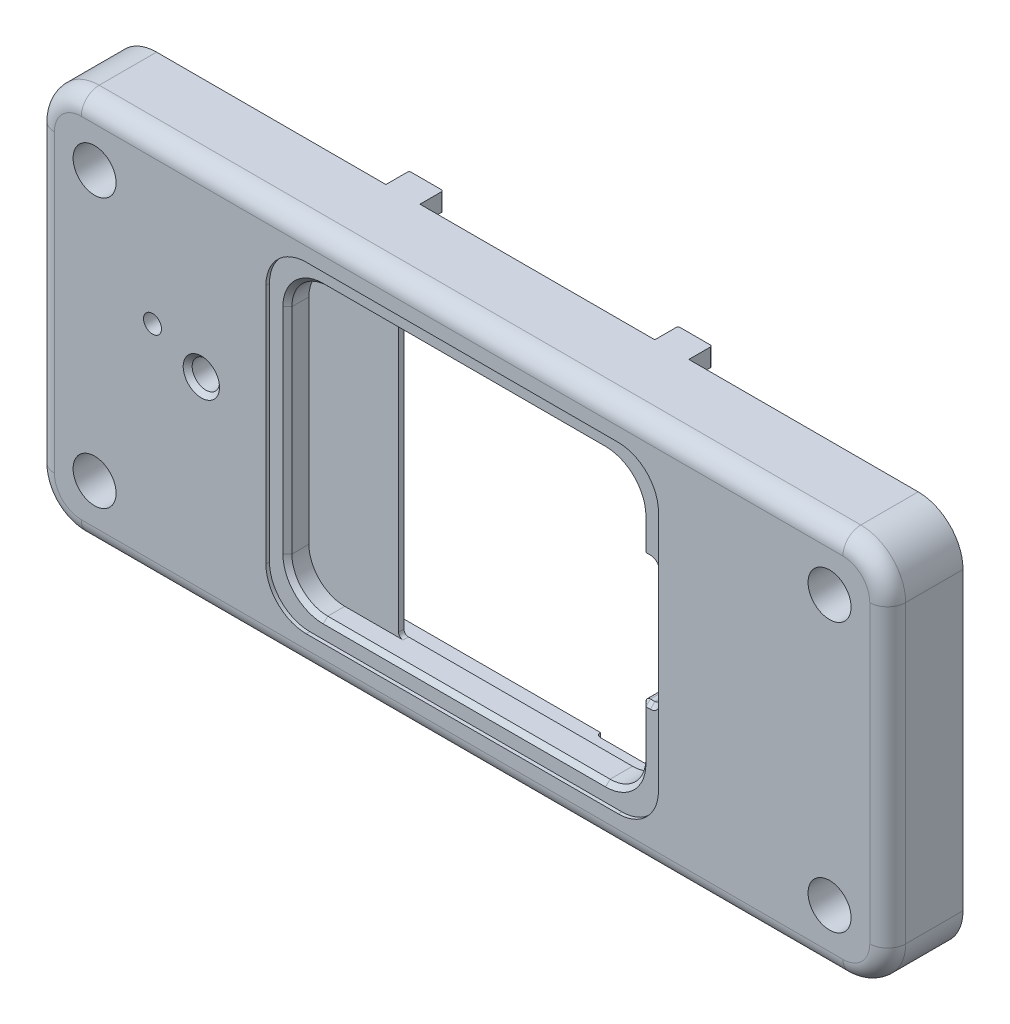
SolidWorks part; units mm, degrees
ref_plane "前视基准面" through (0, 0, 0) normal (0, 0, 1) x (1, 0, 0)
ref_plane "上视基准面" through (0, 0, 0) normal (0, 1, 0) x (1, 0, 0)
ref_plane "右视基准面" through (0, 0, 0) normal (1, 0, 0) x (0, 0, -1)
other "Configuration Table"
sketch "草图2" plane through (0, 0, 0) normal (0, 0, 1) x (1, 0, 0)
  line L0 (81.4875, 0.4873) -> (62.0001, 0.4873) construction
  line L1 (-2.4873, 2.4873) -> (92.4875, 2.4873)
  line L2 (-2.4873, 2.4873) -> (-2.4873, -40.4874)
  line L3 (-2.4873, -40.4874) -> (92.4875, -40.4874)
  line L4 (92.4875, 2.4873) -> (92.4875, -40.4874)
  line L5 (-0.4873, 0.4873) -> (90.4875, 0.4873)
  line L6 (-0.4873, 0.4873) -> (-0.4873, -38.4874)
  line L7 (-0.4873, -38.4874) -> (90.4875, -38.4874)
  line L8 (90.4875, 0.4873) -> (90.4875, -38.4874)
  line L9 (-0.4873, -8.5127) -> (-0.4873, -29.4874) construction
  line L10 (8.5127, -38.4874) -> (52.0301, -38.4874) construction
  line L11 (90.4875, -29.4874) -> (90.4875, -8.5127) construction
  point P10 (0, 0)
  point P13 (0, 0)
extrude "凸台-拉伸1" add sketch "草图2" along normal blind 5
sketch "草图3" plane through (0, 0, 5) normal (0, 0, 1) x (1, 0, 0)
  line L1 (-2.4873, 2.4873) -> (92.4875, 2.4873)
  line L2 (-2.4873, 2.4873) -> (-2.4873, -40.4874)
  line L3 (-2.4873, -40.4874) -> (92.4875, -40.4874)
  line L4 (92.4875, 2.4873) -> (92.4875, -40.4874)
extrude "凸台-拉伸2" add sketch "草图3" along normal blind 3.4
sketch "草图4" plane through (0, 0, 8.4) normal (0, 0, 1) x (1, 0, 0)
  line L0 (0.0127, -9) -> (0.0127, -2) construction
  line L1 (23.1127, -1.0627) -> (66.9127, -1.0627)
  line L2 (23.1127, -1.0627) -> (23.1127, -36.9627)
  line L3 (23.1127, -36.9627) -> (66.9127, -36.9627)
  line L4 (66.9127, -1.0627) -> (66.9127, -36.9627)
  line L5 (2, -0.0127) -> (88.0002, -0.0127) construction
  dimension "D1" = 35.9
  dimension "D2" = 43.8
  dimension "D3" = 23.1
  dimension "D4" = 1.05
extrude "切除-拉伸1" cut sketch "草图4" against normal blind 0.4
fillet "圆角1" radius 4.5 4 edges at (66.9127, -36.9627, 8.2) (23.1127, -36.9627, 8.2) (66.9127, -1.0627, 8.2) (23.1127, -1.0627, 8.2)
sketch "草图5" plane through (0, 0, 8) normal (0, 0, 1) x (1, 0, 0)
  line L0 (62.4127, -1.0627) -> (27.6127, -1.0627) construction
  line L1 (25.1127, -3.0627) -> (64.6127, -3.0627)
  line L2 (25.1127, -3.0627) -> (25.1127, -34.9627)
  line L3 (25.1127, -34.9627) -> (64.6127, -34.9627)
  line L4 (64.6127, -3.0627) -> (64.6127, -11.0627)
  line L5 (27.6127, -36.9627) -> (62.4127, -36.9627) construction
  line L6 (23.1127, -5.5627) -> (23.1127, -32.4627) construction
  line L7 (66.9127, -32.4627) -> (66.9127, -5.5627) construction
  line L8 (64.6127, -11.0627) -> (66.1127, -11.0627)
  line L9 (66.1127, -11.0627) -> (66.1127, -24.9627)
  line L10 (66.1127, -24.9627) -> (64.6127, -24.9627)
  line L11 (64.6127, -24.9627) -> (64.6127, -34.9627)
  dimension "D1" = 2
  dimension "D2" = 2
  dimension "D3" = 2
  dimension "D4" = 2.3
  dimension "D5" = 10
  dimension "D6" = 8
  dimension "D7" = 1.5
extrude "切除-拉伸2" cut sketch "草图5" against normal blind 2.4
sketch "草图6" plane through (0, 0, 5.6) normal (0, 0, 1) x (1, 0, 0)
  line L7 (64.6127, -3.0627) -> (25.1127, -3.0627) construction
  line L8 (35.1127, -3.0627) -> (64.6127, -3.0627)
  line L9 (35.1127, -3.0627) -> (35.1127, -34.9627)
  line L10 (35.1127, -34.9627) -> (64.6127, -34.9627)
  line L11 (64.6127, -3.0627) -> (64.6127, -11.0627)
  line L12 (25.1127, -3.0627) -> (25.1127, -34.9627) construction
  line L13 (64.6127, -11.0627) -> (64.6127, -3.0627) construction
  line L14 (64.6127, -11.0627) -> (66.1127, -11.0627)
  line L15 (66.1127, -11.0627) -> (66.1127, -24.9627)
  line L16 (66.1127, -24.9627) -> (64.6127, -24.9627)
  line L17 (64.6127, -24.9627) -> (64.6127, -34.9627)
  dimension "D1" = 10
extrude "切除-拉伸3" cut sketch "草图6" against normal blind 0.6
fillet "圆角2" radius 4 4 edges at (25.1127, -3.0627, 6.8) (25.1127, -34.9627, 6.8) (64.6127, -3.0627, 6.5) (64.6127, -34.9627, 6.5)
fillet "圆角3" radius 0.5 6 edges at (35.1127, -3.0627, 5.3) (66.1127, -24.9627, 6.5) (66.1127, -11.0627, 6.5) (64.6127, -11.0627, 6.5) (64.6127, -24.9627, 6.5) (35.1127, -34.9627, 5.3)
chamfer "倒角1" distance 0.5 angle 45 16 edges at (65.9663, -24.8163, 8) (65.3627, -24.9627, 8) (66.1127, -18.0127, 8) (64.7591, -25.1091, 8) (65.9663, -11.2091, 8) (64.6127, -28.2127, 8) (65.3627, -11.0627, 8) (63.4411, -33.7911, 8) (64.7591, -10.9163, 8) (44.8627, -34.9627, 8) (64.6127, -8.8127, 8) (26.2843, -33.7911, 8) (63.4411, -4.2343, 8) (25.1127, -19.0127, 8) (44.8627, -3.0627, 8) (26.2843, -4.2343, 8)
sketch "草图7" plane through (0, 2.4873, 0) normal (0, 1, 0) x (1, 0, 0)
  line L0 (92.4875, 0) -> (-2.4873, 0) construction
  line L1 (28.1001, 0) -> (31.9001, 0)
  line L2 (28.1001, 0) -> (28.1001, 2.6)
  line L3 (28.1001, 2.6) -> (31.9001, 2.6)
  line L4 (31.9001, 0) -> (31.9001, 2.6)
  line L5 (28.0001, 5.6) -> (28.0001, 0) construction
  line L6 (32.0001, 0) -> (32.0001, 5.6) construction
  line L7 (58.0001, 5.6) -> (58.0001, 0) construction
  line L8 (58.1001, 0) -> (61.9001, 0)
  line L9 (58.1001, 0) -> (58.1001, 2.6)
  line L10 (58.1001, 2.6) -> (61.9001, 2.6)
  line L11 (61.9001, 0) -> (61.9001, 2.6)
  line L12 (62.0001, 0) -> (62.0001, 5.6) construction
  arc A0 (30.0001, 2.8) -> (30.0001, 6.4) centre (30.0001, 4.6) ccw construction
  arc A1 (60.0001, 2.8) -> (60.0001, 6.4) centre (60.0001, 4.6) ccw construction
  dimension "D6" = 2
  dimension "D1" = 0.1
  dimension "D2" = 0.1
  dimension "D3" = 2
  dimension "D4" = 0.1
  dimension "D5" = 0.1
extrude "凸台-拉伸3" add sketch "草图7" against normal blind 2
fillet "圆角4" radius 0.2 4 edges at (58.1001, 1.4873, -2.6) (61.9001, 1.4873, -2.6) (31.9001, 1.4873, -2.6) (28.1001, 1.4873, -2.6)
sketch "草图8" plane through (0, -40.4874, 0) normal (0, -1, 0) x (1, 0, 0)
  line L1 (52.0301, 0) -> (61.9701, 0)
  line L2 (52.0301, 0) -> (52.0301, 0.5)
  line L3 (52.0301, 0.5) -> (61.9701, 0.5)
  line L4 (61.9701, 0) -> (61.9701, 0.5)
  line L5 (-2.4873, 0) -> (92.4875, 0) construction
  line L8 (61.4701, -1.35) -> (61.4701, -2.01) construction
  line L9 (52.5301, -1.35) -> (52.5301, -2.01) construction
  point P6 (61.4701, 0.5)
  point P13 (0, 0)
  dimension "D1" = 0.5
  dimension "D2" = 0.5
  dimension "D3" = 0.5
extrude "切除-拉伸4" cut sketch "草图8" against normal blind 2
sketch "草图9" plane through (0, -40.4874, 0) normal (0, -1, 0) x (1, 0, 0)
  line L1 (68.6664, 0) -> (74.8952, 0)
  line L2 (68.6664, 0) -> (68.6664, -1.5)
  line L3 (68.6664, -1.5) -> (74.8952, -1.5)
  line L4 (74.8952, 0) -> (74.8952, -1.5)
  line L5 (68.5664, 0) -> (68.5664, -3.6) construction
  line L6 (61.9701, 0) -> (92.4875, 0) construction
  line L7 (74.9952, -3.6) -> (74.9952, 0) construction
  point P7 (0, 0)
  point P9 (0, 0)
  point P12 (0, 0)
  point P13 (74.9952, -0.9934)
  point P14 (0, 0)
  point P15 (0, 0)
  dimension "D1" = 0.1
  dimension "D2" = 0.1
  dimension "D3" = 1.5
extrude "凸台-拉伸4" add sketch "草图9" against normal blind 2
fillet "圆角5" radius 0.3 2 edges at (68.6664, -39.4874, -1.5) (74.8952, -39.4874, -1.5)
fillet "圆角6" radius 0.5 2 edges at (52.0301, -39.4874, 0.5) (61.9701, -39.4874, 0.5)
chamfer "倒角3" distance 1 angle 55 3 edges at (61.8237, -40.4874, 0.3536) (52.1766, -40.4874, 0.3536) (57.0001, -40.4874, 0.5) first distance on face at (59.9061, -40.4874, 0.8916)
sketch "草图11" plane through (0, 0, 8.4) normal (0, 0, 1) x (1, 0, 0)
  circle A0 centre (15.9127, -17.9985) radius 1.525
  circle A1 centre (10.464, -15.5857) radius 1
  dimension "D1" = 3.05
  dimension "D2" = 2
extrude "切除-拉伸5" cut sketch "草图11" against normal through all
chamfer "倒角4" distance 0.5 angle 45 1 edges at (17.4377, -17.9985, 8.4)
sketch "草图13" plane through (0, 0, 5) normal (0, 0, -1) x (-1, 0, 0)
  line L0 (-86.4875, -8.5127) -> (-90.4875, -8.5127) construction
  line L1 (-90.4875, 0.4873) -> (-81.4875, 0.4873)
  line L2 (-90.4875, 0.4873) -> (-90.4875, -8.5127)
  line L3 (-90.4875, -8.5127) -> (-81.4875, -8.5127)
  line L4 (-81.4875, 0.4873) -> (-81.4875, -8.5127)
  line L5 (-90.4875, -38.4874) -> (-81.4875, -38.4874)
  line L6 (-90.4875, -38.4874) -> (-90.4875, -29.4874)
  line L7 (-90.4875, -29.4874) -> (-81.4875, -29.4874)
  line L8 (-81.4875, -38.4874) -> (-81.4875, -29.4874)
  line L9 (0.4873, 0.4873) -> (-8.5127, 0.4873)
  line L10 (0.4873, 0.4873) -> (0.4873, -8.5127)
  line L11 (0.4873, -8.5127) -> (-8.5127, -8.5127)
  line L12 (-8.5127, 0.4873) -> (-8.5127, -8.5127)
  line L13 (0.4873, -38.4874) -> (-8.5127, -38.4874)
  line L14 (0.4873, -38.4874) -> (0.4873, -29.4874)
  line L15 (0.4873, -29.4874) -> (-8.5127, -29.4874)
  line L16 (-8.5127, -38.4874) -> (-8.5127, -29.4874)
  line L17 (0.4873, -8.5127) -> (-3.5127, -8.5127) construction
  line L18 (-8.5127, -3.5127) -> (-8.5127, 0.4873) construction
  line L19 (-3.5127, -29.4874) -> (0.4873, -29.4874) construction
  line L20 (-8.5127, -38.4874) -> (-8.5127, -34.4874) construction
  line L21 (-90.4875, -29.4874) -> (-86.4875, -29.4874) construction
  line L22 (-81.4875, -34.4874) -> (-81.4875, -38.4874) construction
extrude "凸台-拉伸5" add sketch "草图13" along normal blind 3.3
fillet "圆角7" radius 5 4 edges at (8.5127, -29.4874, 3.35) (81.4875, -29.4874, 3.35) (81.4875, -8.5127, 3.35) (8.5127, -8.5127, 3.35)
sketch "草图12" plane through (0, 0, 8.4) normal (0, 0, 1) x (1, 0, 0)
  circle A0 centre (4, -4) radius 2.4
  circle A1 centre (86.0002, -4) radius 2.4
  circle A2 centre (86.0002, -34.0001) radius 2.4
  circle A3 centre (4, -34.0001) radius 2.4
  dimension "D1" = 4.8
extrude "切除-拉伸6" cut sketch "草图12" against normal blind 5
sketch "草图14" plane through (0, 0, 3.4) normal (0, 0, 1) x (1, 0, 0)
  circle A0 centre (4, -4) radius 1.4
  circle A1 centre (86.0002, -4) radius 1.4
  circle A2 centre (86.0002, -34.0001) radius 1.4
  circle A3 centre (4, -34.0001) radius 1.4
  dimension "D1" = 2.8
extrude "切除-拉伸7" cut sketch "草图14" against normal through all
fillet "圆角8" radius 5 4 edges at (-2.4873, 2.4873, 4.2) (-2.4873, -40.4874, 4.2) (92.4875, -40.4874, 4.2) (92.4875, 2.4873, 4.2)
fillet "圆角9" radius 2 8 edges at (-1.0228, -39.0229, 8.4) (-2.4873, -19, 8.4) (-1.0228, 1.0228, 8.4) (45.0001, 2.4873, 8.4) (91.023, 1.0228, 8.4) (92.4875, -19, 8.4) (91.023, -39.0229, 8.4) (45.0001, -40.4874, 8.4)
fillet "圆角10" radius 2 4 edges at (90.4875, 0.4873, 0.85) (90.4875, -38.4874, 0.85) (-0.4873, -38.4874, 0.85) (-0.4873, 0.4873, 0.85)
